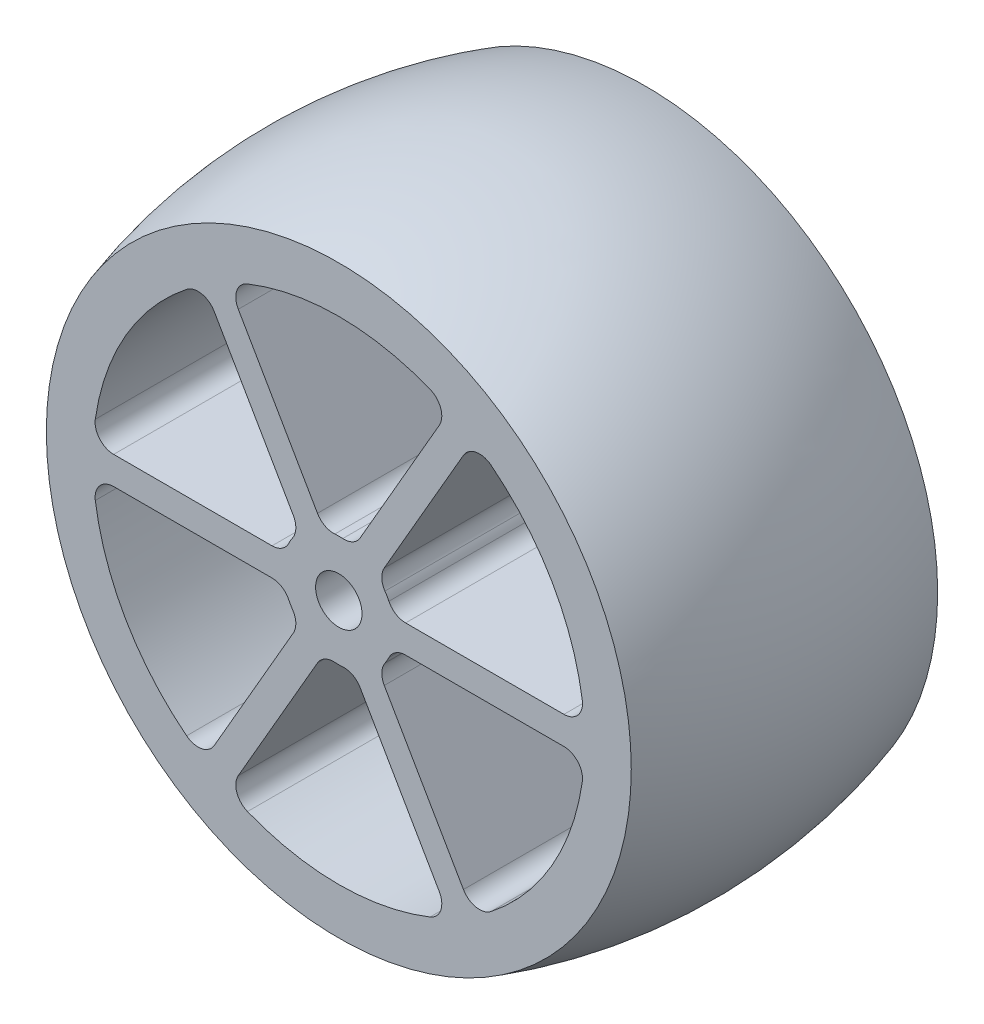
SolidWorks part; units mm, degrees
material "ABS"
ref_plane "Ebene vorne" through (0, 0, 0) normal (0, 0, 1) x (1, 0, 0)
ref_plane "Ebene oben" through (0, 0, 0) normal (0, 1, 0) x (1, 0, 0)
ref_plane "Ebene rechts" through (0, 0, 0) normal (1, 0, 0) x (0, 0, -1)
ref_axis "Achse1" through (0, 0, 18.15) along (0, 0, -1)
sketch "Skizze4" plane through (0, 0, 0) normal (1, 0, 0) x (0, 0, -1)
  line L0 (-6.7395, 0) -> (20.4729, 0) construction
  line L1 (0, 34) -> (0, 0) construction
  line L2 (-16.5, 31.5) -> (-16.5, 0)
  line L3 (-16.5, 0) -> (16.5, 0)
  line L4 (16.5, 0) -> (16.5, 31.5)
  arc A0 (-16.5, 31.5) -> (16.5, 31.5) centre (0, -21.7) cw
  dimension "D1" = 68
  dimension "D2" = 2.5
  dimension "D3" = 33
revolve "Rotation1" add sketch "Skizze4" angle 360 about L0
sketch "Skizze5" plane through (0, 0, 16.5) normal (0, 0, 1) x (1, 0, 0)
  line L0 (0, 0) -> (15.75, 27.2798) construction
  line L1 (0, 0) -> (-15.75, 27.2798) construction
  line L2 (0, 0) -> (0, 31.5) construction
  line L3 (-11.9297, 23.6629) -> (-1.6057, 5.7812)
  line L4 (11.9297, 23.6629) -> (1.6057, 5.7812)
  circle A0 centre (0, 0) radius 31.5 construction
  arc A1 (-11.9297, 23.6629) -> (11.9297, 23.6629) centre (0, 0) cw
  arc A2 (-1.6057, 5.7812) -> (1.6057, 5.7812) centre (0, 0) cw
  dimension "D2" = 6
  dimension "D3" = 5
  dimension "D1" = 60
  dimension "D4" = 3
extrude "Schnitt-Linear austragen1" cut sketch "Skizze5" against normal through all
fillet "Verrundung1" radius 2 4 edges at (11.9297, 23.6629, 0) (1.6057, 5.7812, 0) (-1.6057, 5.7812, 0) (-11.9297, 23.6629, 0)
pattern_circular "Kreismuster1" count 6 over 360 about axis through (0, 0, 18.15) along (0, 0, -1) of "Schnitt-Linear austragen1", "Verrundung1"
sketch "Skizze7" plane through (0, 0, 16.5) normal (0, 0, 1) x (1, 0, 0)
  circle A0 centre (0, 0) radius 2.5
  dimension "D1" = 5
extrude "Schnitt-Linear austragen3" cut sketch "Skizze7" against normal through all
